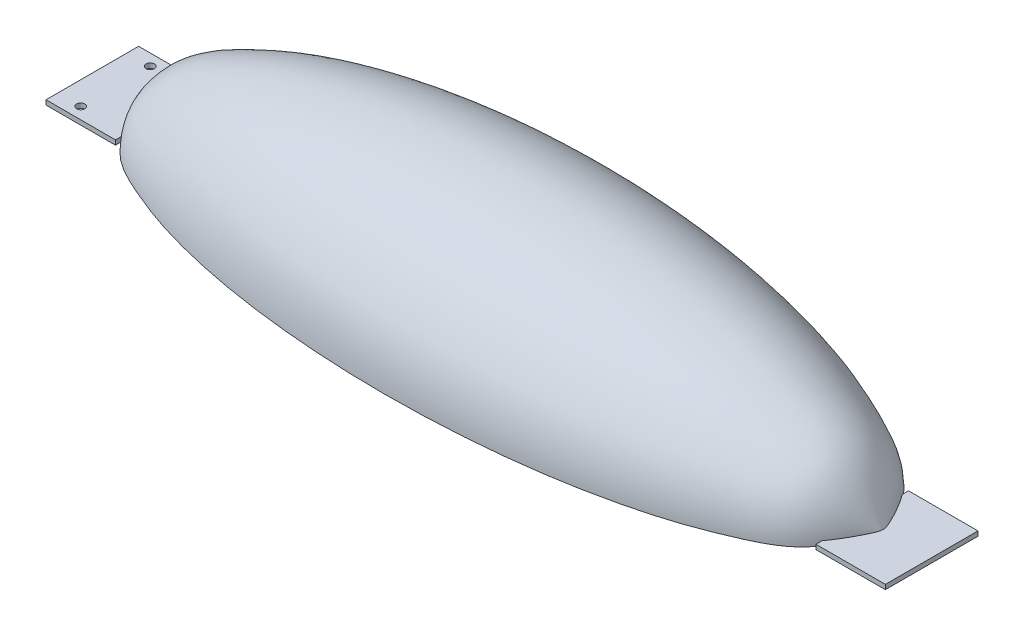
SolidWorks part; units mm, degrees
ref_plane "Front Plane" through (0, 0, 0) normal (0, 0, 1) x (1, 0, 0)
ref_plane "Top Plane" through (0, 0, 0) normal (0, 1, 0) x (1, 0, 0)
ref_plane "Right Plane" through (0, 0, 0) normal (1, 0, 0) x (0, 0, -1)
sketch "Sketch1" plane through (0, 0, 0) normal (0, 0, 1) x (1, 0, 0)
  line L0 (-322.5, 0) -> (0, 0)
  line L1 (10, 0) -> (-332.5, 0) construction
  spline S0 degree 3 poles (0, 0) (-4.444, 8.959) (-11.7302, 23.6481) (-31.9295, 33.0481) (-48.096, 39.4847) (-64.3821, 44.1353) (-80.5411, 47.7584) (-96.6987, 50.5186) (-112.8411, 52.5685) (-128.9798, 53.9846) (-145.1154, 54.8169) (-161.25, 55.0915) (-177.3846, 54.8169) (-193.5202, 53.9846) (-209.6589, 52.5685) (-225.8013, 50.5186) (-241.9589, 47.7584) (-258.1179, 44.1353) (-274.404, 39.4847) (-290.5705, 33.0481) (-310.7698, 23.6481) (-318.056, 8.959) (-322.5, 0) knots 0 0 0 0 0.080666 0.132259 0.180571 0.227482 0.273629 0.319312 0.364698 0.409893 0.454973 0.5 0.545027 0.590107 0.635302 0.680688 0.726371 0.772518 0.819429 0.867741 0.919334 1 1 1 1
revolve "Revolve1" add sketch "Sketch1" angle 360 about L1
sketch "Sketch2" plane through (0, 0, 0) normal (0, 1, 0) x (1, 0, 0)
  line L0 (-372.5, 80) -> (50, 80)
  line L1 (50, 80) -> (50, -80)
  line L2 (50, -80) -> (-372.5, -80)
  line L3 (-372.5, -80) -> (-372.5, 80)
extrude "Cut-Extrude1" cut sketch "Sketch2" against normal blind 80
sketch "Sketch3" plane through (0, 0, 0) normal (0, 1, 0) x (1, 0, 0)
  line L0 (-342.5, 20) -> (-312.5, 20)
  line L1 (-312.5, 20) -> (-312.5, -20)
  line L2 (-312.5, -20) -> (-342.5, -20)
  line L3 (-342.5, -20) -> (-342.5, 20)
  line L4 (-10, 20) -> (20, 20)
  line L5 (20, 20) -> (20, -20)
  line L6 (20, -20) -> (-10, -20)
  line L7 (-10, -20) -> (-10, 20)
extrude "Boss-Extrude1" add sketch "Sketch3" along normal blind 2
sketch "Sketch4" plane through (0, 0, 0) normal (0, 1, 0) x (1, 0, 0)
  circle A0 centre (-332.5, -15) radius 1.8
  circle A1 centre (-332.5, 15) radius 1.8
extrude "Cut-Extrude2" cut sketch "Sketch4" along normal blind 3
